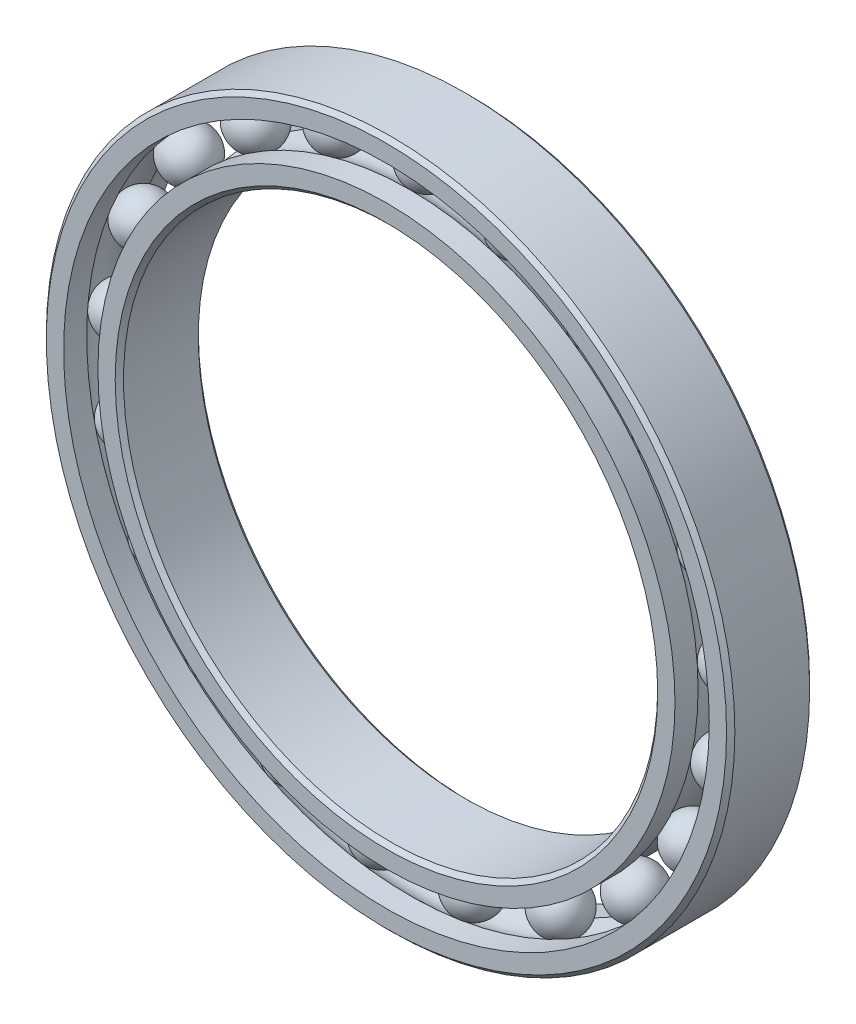
SolidWorks part; units mm, degrees
ref_plane "Front Plane" through (0, 0, 0) normal (0, 0, 1) x (1, 0, 0)
ref_plane "Top Plane" through (0, 0, 0) normal (0, 1, 0) x (1, 0, 0)
ref_plane "Right Plane" through (0, 0, 0) normal (1, 0, 0) x (0, 0, -1)
sketch "Sketch1" plane through (0, 0, 0) normal (0, 0, 1) x (1, 0, 0)
  circle A0 centre (0, 0) radius 29
  circle A1 centre (0, 0) radius 22.5
  dimension "OD" = 58
  dimension "ID" = 45
sketch "Sketch5" plane through (0, 0, 0) normal (1, 0, 0) x (0, 0, -1)
  line L0 (-3.5, 0) -> (3.5, 0) construction
  line L1 (0, 29) -> (0, -29) construction
  line L2 (3.15, 29) -> (-3.15, 29)
  line L3 (-3.15, 29) -> (-3.5, 28.65)
  line L4 (-3.5, 28.65) -> (-3.5, 27.1944)
  line L5 (-3.5, 27.1944) -> (-1.5556, 27.1944)
  line L6 (3.5, 27.1944) -> (1.5556, 27.1944)
  line L7 (3.5, 28.65) -> (3.5, 27.1944)
  line L8 (3.15, 29) -> (3.5, 28.65)
  line L9 (0, 29) -> (0, 25.75) construction
  line L10 (0, 25.75) -> (0, 22.5) construction
  line L11 (-2.1228, 25.75) -> (-3.5, 25.75) construction
  line L12 (2.6209, 24.331) -> (3.0019, 24.331) construction
  line L13 (-2.6209, 24.331) -> (-3.0019, 24.331) construction
  line L14 (-2.6209, 24.331) -> (-2.6209, 27.169) construction
  line L15 (-2.6209, 27.169) -> (-3.0019, 27.169) construction
  line L16 (-3.0019, 24.331) -> (-3.0019, 27.169) construction
  line L17 (-2.6209, 24.331) -> (-3.0019, 27.169) construction
  line L18 (-2.6209, 27.169) -> (-3.0019, 24.331) construction
  line L19 (3.0019, 24.331) -> (3.0019, 27.169) construction
  line L20 (2.6209, 27.169) -> (3.0019, 27.169) construction
  line L21 (2.6209, 24.331) -> (2.6209, 27.169) construction
  line L22 (0, 29) -> (0, -29) construction
  arc A0 (-1.5556, 27.1944) -> (1.5556, 27.1944) centre (0, 25.75) cw
  circle A1 centre (0, 25.75) radius 2.1228 construction
  point P14 (0, 22.5)
  point P15 (-2.8114, 25.75)
  dimension "Width" = 7
  dimension "D1" = 45
  dimension "D2" = 0.35
  dimension "D3" = 3.1111
  dimension "D4" = 1.4444
  dimension "D5" = 0.381
  dimension "D6" = 0.0254
  dimension "D7" = 7
revolve "Revolve1" add sketch "Sketch5" angle 360 about L0
sketch "Sketch3" plane through (0, 0, 0) normal (1, 0, 0) x (0, 0, -1)
  line L0 (-3.5, 24.3056) -> (-1.5556, 24.3056)
  line L1 (0, 29) -> (0, -29) construction
  line L2 (-3.5, 28.65) -> (-3.5, 27.1944) construction
  line L3 (-3.5, 24.3056) -> (-3.5, 22.85)
  line L4 (-3.15, 29) -> (-3.5, 28.65) construction
  line L5 (-3.5, 22.85) -> (-3.15, 22.5)
  line L6 (-3.15, 22.5) -> (3.15, 22.5)
  line L7 (3.15, 29) -> (3.15, -29) construction
  line L8 (3.15, 22.5) -> (3.5, 22.85)
  line L9 (3.5, -28.65) -> (3.5, 28.65) construction
  line L10 (3.5, 22.85) -> (3.5, 24.3056)
  line L11 (3.5, 24.3056) -> (1.5556, 24.3056)
  line L13 (3.15, 29) -> (3.5, 28.65) construction
  arc A0 (1.5556, 27.1944) -> (-1.5556, 27.1944) centre (0, 25.75) ccw construction
  arc A1 (1.5556, 24.3056) -> (-1.5556, 24.3056) centre (0, 25.75) cw
revolve "Revolve3" add sketch "Sketch3" angle 360 about L0
sketch "Sketch4" plane through (0, 0, 0) normal (1, 0, 0) x (0, 0, -1)
  line L0 (-2.1228, 25.75) -> (2.1228, 25.75)
  arc A2 (-2.1228, 25.75) -> (2.1228, 25.75) centre (0, 25.75) cw
  arc A3 (1.5556, 27.1944) -> (-1.5556, 27.1944) centre (0, 25.75) ccw construction
revolve "Revolve4" add sketch "Sketch4" angle 360 about L0
pattern_circular "CirPattern1" count 21 every 17.143 of bodies 104
ref_axis "Center Axis 1" through (0, 0, -3.15) along (0, 0, 1)
equation "\"D2@Sketch5\" = \"Width@Sketch5\" * .05"
equation "\"D3@Sketch5\" = \"Width@Sketch5\" / 2.25"
equation "\"D4@Sketch5\"=((\"OD@Sketch1\"-\"ID@Sketch1\")/2)/4.5"
equation "\"D2@CirPattern1\" = 360/\"Balls@CirPattern1\""
